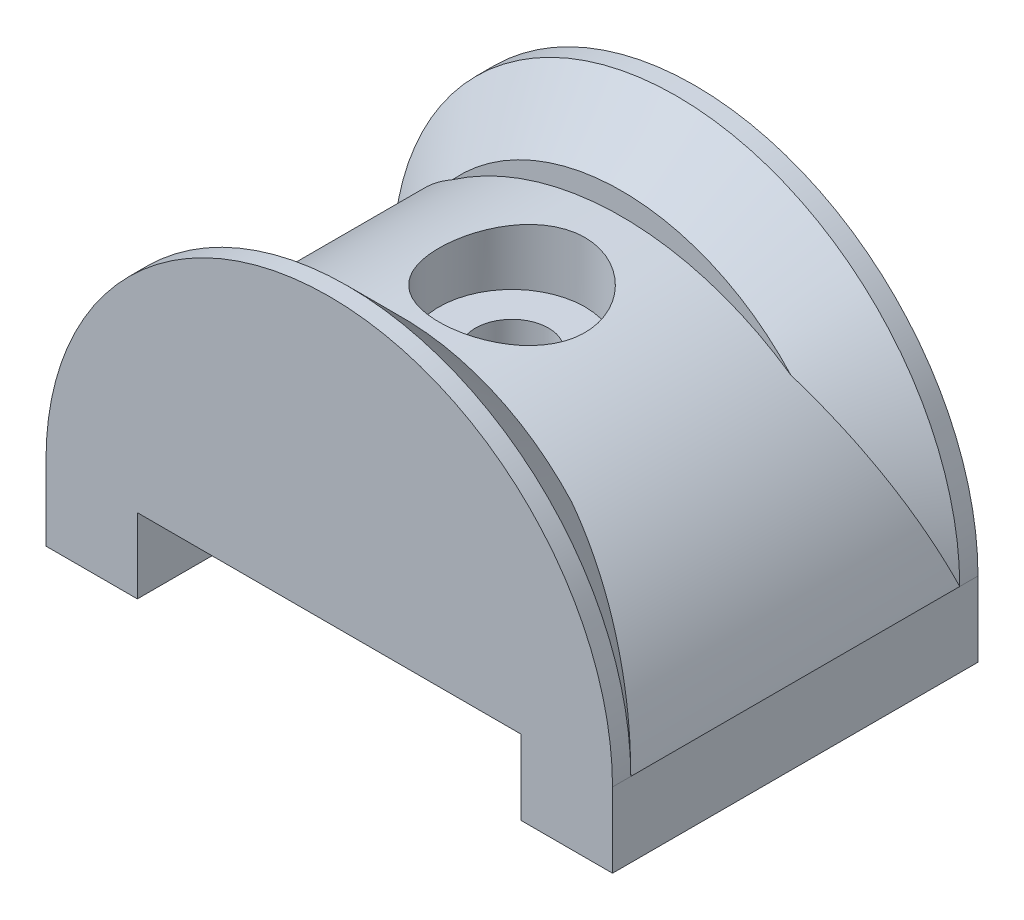
SolidWorks part; units mm, degrees
ref_plane "Plan de face" through (0, 0, 0) normal (0, 0, 1) x (1, 0, 0)
ref_plane "Plan de dessus" through (0, 0, 0) normal (0, 1, 0) x (1, 0, 0)
ref_plane "Plan de droite" through (0, 0, 0) normal (1, 0, 0) x (0, 0, -1)
sketch "Esquisse1" plane through (0, 0, 0) normal (0, 0, 1) x (1, 0, 0)
  line L0 (-9.409, 0) -> (11.591, 0)
  line L1 (-14.409, 0) -> (-9.409, 0)
  line L2 (-14.409, 0) -> (-14.409, -4.0882)
  line L3 (-14.409, -4.0882) -> (-9.409, -4.0882)
  line L4 (-9.409, 0) -> (-9.409, -4.0882)
  line L5 (11.591, 0) -> (16.591, 0)
  line L6 (11.591, 0) -> (11.591, -4.0882)
  line L7 (11.591, -4.0882) -> (16.591, -4.0882)
  line L8 (16.591, 0) -> (16.591, -4.0882)
  arc A1 (-14.409, 0) -> (16.591, 0) centre (1.091, 0) cw
  dimension "D1" = 21
  dimension "D2" = 5
  dimension "D3" = 5
extrude "Boss.-Extru.1" add sketch "Esquisse1" along normal blind 20 contours A1 L1 L0 L5 | L4 L1 L2 L3 | L8 L5 L6 L7 region at (1.091, 6.5784, 0) region at (-11.909, -2.0441, 0) region at (14.091, -2.0441, 0)
sketch "Esquisse2" plane through (0, 0, 20) normal (0, 0, 1) x (1, 0, 0)
  arc A0 (-14.409, 0) -> (16.591, 0) centre (1.091, -5) cw
  arc A1 (16.591, 0) -> (-14.409, 0) centre (1.091, 0) ccw construction
  arc A2 (-14.409, 0) -> (16.591, 0) centre (1.091, 0) cw
  dimension "D1" = 5
extrude "Enlèv. mat.-Extru.1" cut sketch "Esquisse2" against normal blind 12 from offset 4 offset against normal yes
chamfer "Chanfrein1" distance 3 angle 45 2 edges at (1.091, 15.5, 4) (1.091, 15.5, 16)
sketch "Esquisse3" plane through (0, 0, 0) normal (0, -1, 0) x (1, 0, 0)
  line L0 (-9.409, 20) -> (11.591, 20) construction
  line L2 (-14.409, 20) -> (-14.409, 0) construction
  circle A0 centre (1.091, 10) radius 2
  point P7 (-14.409, 10.1814)
  dimension "D1" = 10
  dimension "D2" = 15.5
  dimension "D3" = 4
extrude "Enlèv. mat.-Extru.2" cut sketch "Esquisse3" against normal blind 12
sketch "Esquisse4" plane through (0, 0, 0) normal (0, -1, 0) x (1, 0, 0)
  circle A0 centre (1.091, 10) radius 4
  dimension "D1" = 8
extrude "Enlèv. mat.-Extru.3" cut sketch "Esquisse4" against normal blind 12 from offset 8 offset against normal yes
